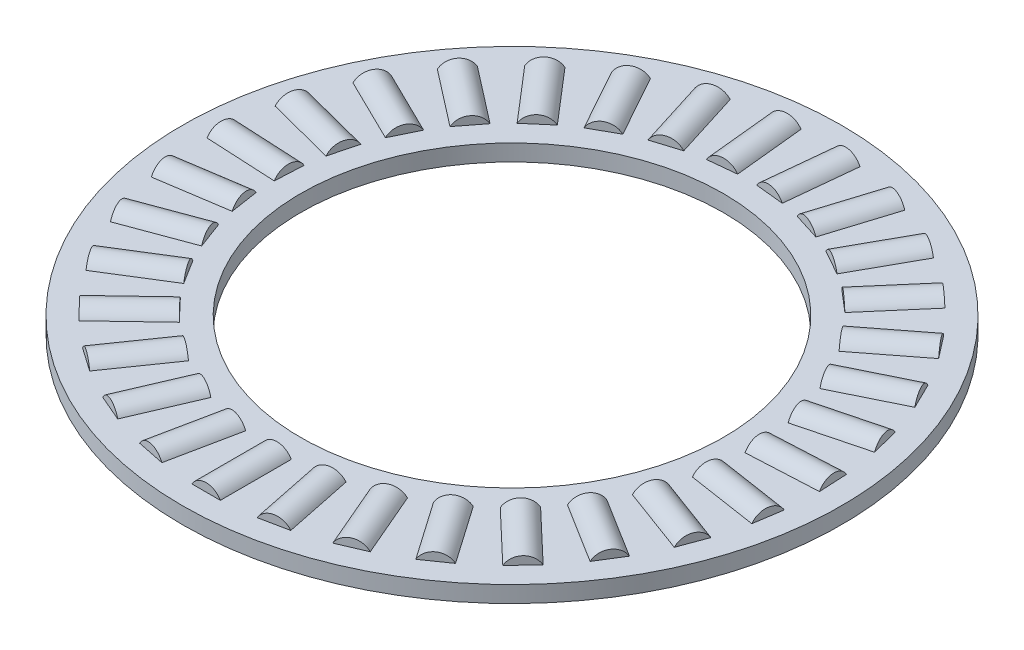
SolidWorks part; units mm, degrees
ref_plane "Front Plane" through (0, 0, 0) normal (0, 0, 1) x (1, 0, 0)
ref_plane "Top Plane" through (0, 0, 0) normal (0, 1, 0) x (1, 0, 0)
ref_plane "Right Plane" through (0, 0, 0) normal (1, 0, 0) x (0, 0, -1)
sketch "Sketch1" plane through (0, 0, 0) normal (1, 0, 0) x (0, 0, -1)
  line L0 (-19.8438, 0) -> (19.8438, 0) construction
  line L1 (0, -0.9922) -> (0, 0.9922) construction
  line L2 (-19.8438, 0.4961) -> (-12.7254, 0.4961)
  line L3 (-19.8438, 0.4961) -> (-19.8438, -0.4961)
  line L4 (-19.8438, -0.4961) -> (-12.7254, -0.4961)
  line L5 (-12.7254, 0.4961) -> (-12.7254, -0.4961)
  line L7 (-16.2846, 0.9922) -> (-16.2846, 0.4961) construction
  line L8 (-18.4201, 0.9922) -> (-14.1491, 0.9922) construction
  line L9 (-18.4201, 0.9922) -> (-18.4201, -0.9922) construction
  line L10 (-18.4201, -0.9922) -> (-14.1491, -0.9922) construction
  line L11 (-14.1491, 0.9922) -> (-14.1491, -0.9922) construction
  line L12 (19.8438, 0.9922) -> (19.8438, -0.9922) construction
  point P16 (-18.4201, 0)
  point P21 (19.8438, 0)
  dimension "OD" = 39.6875
  dimension "ID" = 25.4508
  dimension "Washer Thickness" = 0.9922
  dimension "D1" = 4.271
  dimension "Thickness" = 1.9844
sketch "Sketch6" plane through (0, 0, 0) normal (0, 1, 0) x (1, 0, 0)
  circle A0 centre (0, 0) radius 19.8438 construction
  circle A1 centre (0, 0) radius 12.7254 construction
  circle A2 centre (0, 0) radius 12.7 construction
  dimension "For Shaft Diameter" = 25.4
  dimension "OD" = 39.6875
  dimension "ID" = 25.4508
sketch "Sketch5" plane through (0, 0, 0) normal (1, 0, 0) x (0, 0, -1)
  line L1 (-19.8438, 0.4961) -> (-12.7254, 0.4961)
  line L2 (-19.8438, 0.4961) -> (-19.8438, -0.4961)
  line L3 (-19.8438, -0.4961) -> (-12.7254, -0.4961)
  line L4 (-12.7254, 0.4961) -> (-12.7254, -0.4961)
revolve "Revolve3" add sketch "Sketch5" angle 360 about L1
sketch "Sketch3" plane through (0, 0, 0) normal (1, 0, 0) x (0, 0, -1)
  line L0 (-18.4201, 0.9922) -> (-18.4201, -0.9922) construction
  line L1 (-18.4201, 0) -> (-14.1491, 0)
  line L2 (-18.4201, 0) -> (-18.4201, 0.9922)
  line L3 (-18.4201, 0.9922) -> (-14.1491, 0.9922)
  line L4 (-14.1491, 0) -> (-14.1491, 0.9922)
revolve "Cut-Revolve1" cut sketch "Sketch3" angle 360 about L1
sketch "Sketch2" plane through (0, 0, 0) normal (1, 0, 0) x (0, 0, -1)
  line L1 (-18.4201, 0) -> (-14.1491, 0)
  line L2 (-18.4201, 0) -> (-18.4201, 0.9922)
  line L3 (-18.4201, 0.9922) -> (-14.1491, 0.9922)
  line L4 (-14.1491, 0) -> (-14.1491, 0.9922)
revolve "Revolve2" add sketch "Sketch2" angle 360 about L1
ref_axis "Axis1" through (0, 0.9922, 0) along (0, -1, 0)
pattern_circular "CirPattern1" count 31 every 11.613 about axis through (0, 0.9922, 0) along (0, -1, 0) of bodies 187 411
pattern_circular "CirPattern2" count 31 every 11.613 about axis through (0, 0, 0) along (0, 1, 0) of "Cut-Revolve1"
equation "\"Rollers@CirPattern1\"= \"OD@Sketch1\" * 20"
equation "\"Angle@CirPattern1\" = 360/\"Rollers@CirPattern1\""
equation "\"D1@CirPattern2\" = \"Rollers@CirPattern1\""
equation "\"D2@CirPattern2\" = \"Angle@CirPattern1\""
equation "\"D1@Sketch1\"=((\"OD@Sketch1\"-\"ID@Sketch1\")/2)*.6"
